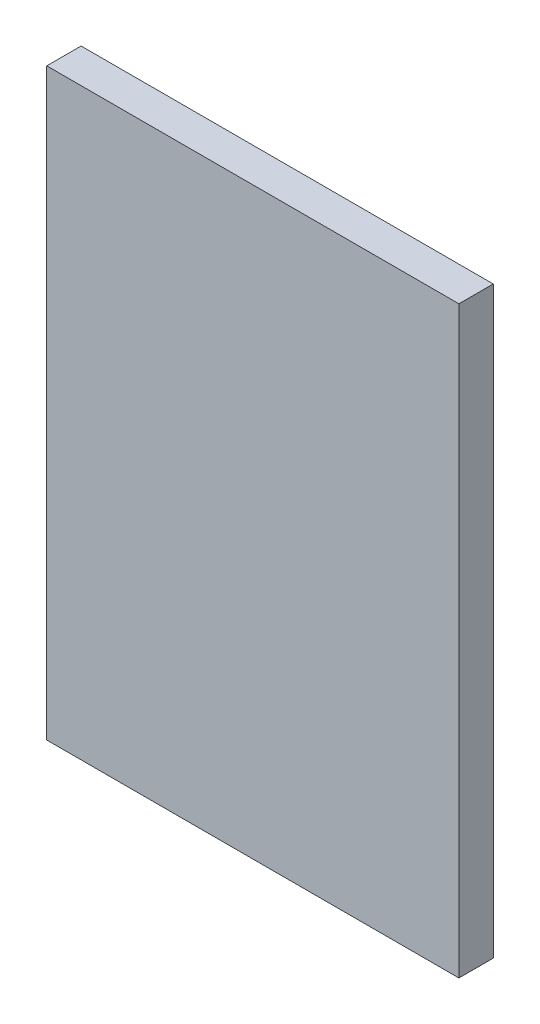
SolidWorks part; units mm, degrees
ref_plane "Front Plane" through (0, 0, 0) normal (0, 0, 1) x (1, 0, 0)
ref_plane "Top Plane" through (0, 0, 0) normal (0, 1, 0) x (1, 0, 0)
ref_plane "Right Plane" through (0, 0, 0) normal (1, 0, 0) x (0, 0, -1)
sketch "Sketch1" plane through (0, 0, 0) normal (0, 0, 1) x (1, 0, 0)
  line L0 (-13.9789, -31.4581) -> (-13.9789, 1.1797) construction
  line L1 (-12.5349, 25.527) -> (47.4651, 25.527)
  line L2 (-12.5349, 25.527) -> (-12.5349, -59.473)
  line L3 (-12.5349, -59.473) -> (47.4651, -59.473)
  line L4 (47.4651, 25.527) -> (47.4651, -59.473)
  line L5 (-13.9789, -31.4581) -> (-13.9789, 1.1797)
  line L6 (-17.5349, -26.7013) -> (-17.5349, -15.1448) construction
  line L7 (-17.5349, -26.7013) -> (-17.5349, -15.1448)
  line L8 (-12.5349, 25.527) -> (-12.5349, -25.527) construction
  line L9 (-4.45, 25.527) -> (-12.5349, 25.527) construction
  line L10 (-12.5349, 25.527) -> (-12.5349, -25.527)
  line L11 (-4.45, 25.527) -> (-12.5349, 25.527)
  dimension "D1" = 60
  dimension "D2" = 85
extrude "Boss-Extrude1" add sketch "Sketch1" along normal blind 5 contours L4 L3 L2 L1
